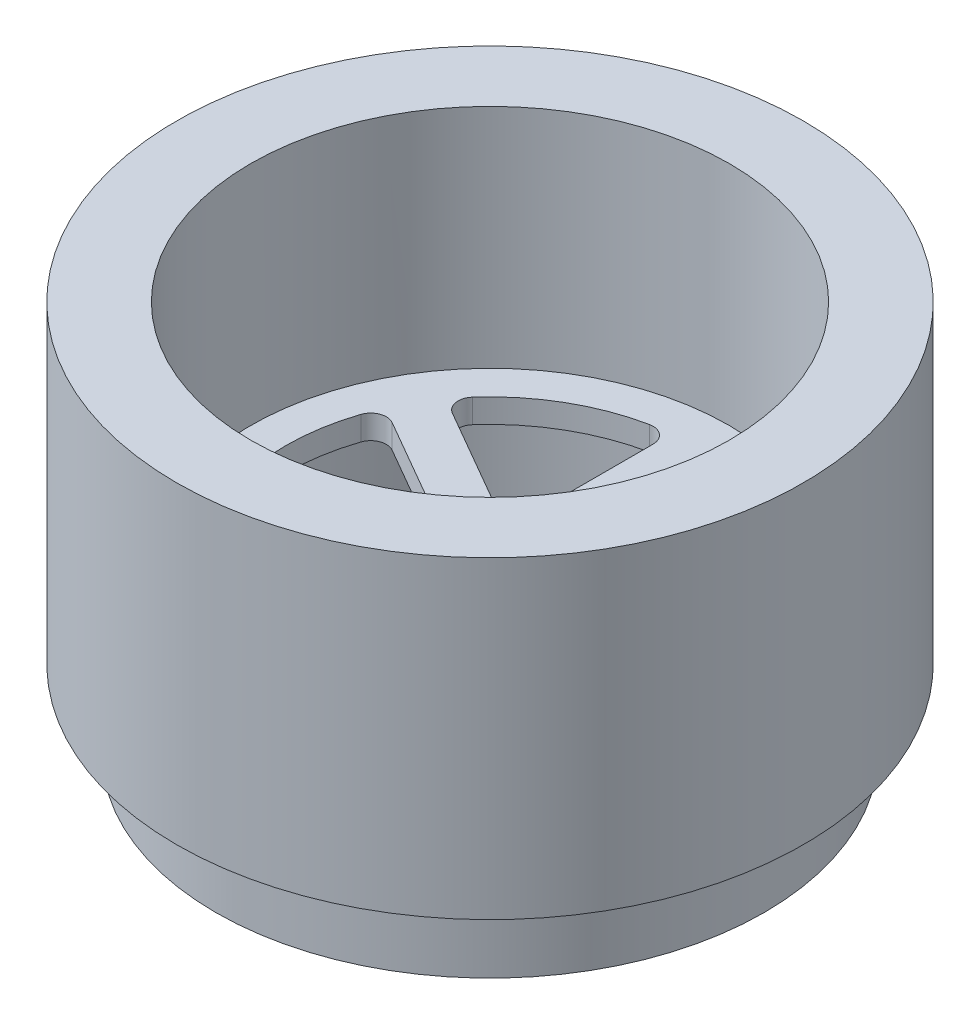
SolidWorks part; units mm, degrees
material "6061-T6 (SS)"
ref_plane "Front Plane" through (0, 0, 0) normal (0, 0, 1) x (1, 0, 0)
ref_plane "Top Plane" through (0, 0, 0) normal (0, 1, 0) x (1, 0, 0)
ref_plane "Right Plane" through (0, 0, 0) normal (1, 0, 0) x (0, 0, -1)
other "Center of Mass"
sketch "Sketch1" plane through (0, 0, 0) normal (0, 1, 0) x (1, 0, 0)
  circle A0 centre (0, 0) radius 20
  circle A1 centre (0, 0) radius 15.28
  dimension "D1" = 30.56
  dimension "D2" = 40
extrude "Boss-Extrude1" add sketch "Sketch1" along normal blind 25
ref_plane "Plane1" through (0, 9, 0) normal (0, -1, 0) x (-1, 0, 0)
sketch "Sketch3" plane through (0, 9, 0) normal (0, -1, 0) x (-1, 0, 0)
  circle A0 centre (0, 0) radius 20
  dimension "D1" = 40
extrude "Boss-Extrude2" add sketch "Sketch3" against normal blind 1.524
sketch "Sketch4" plane through (0, 9, 0) normal (0, -1, 0) x (-1, 0, 0)
  circle A0 centre (0, 0) radius 0.756
  circle A1 centre (0, 0) radius 2
  dimension "D1" = 1.512
extrude "Boss-Extrude3" add sketch "Sketch4" along normal blind 3.5
sketch "Sketch5" plane through (0, 0, 0) normal (0, 1, 0) x (1, 0, 0)
  circle A0 centre (0, 0) radius 17.5
  dimension "D1" = 35
extrude "Cut-Extrude1" cut sketch "Sketch5" along normal blind 5 flip side to cut
sketch "Sketch6" plane through (0, 9, 0) normal (0, -1, 0) x (-1, 0, 0)
  line L0 (1.4079, -4.359) -> (1.4079, -11.8075)
  line L1 (0, 0) -> (6.5253, -11.3021) construction
  line L2 (3.071, -3.3987) -> (9.5217, -7.123)
  circle A0 centre (0, 0) radius 13.0506 construction
  circle A1 centre (0, 0) radius 3.9798 construction
  arc A2 (2.6077, -12.7874) -> (9.7703, -8.652) centre (0, 0) ccw
  arc A3 (1.9243, -3.4836) -> (2.0547, -3.4083) centre (0, 0) ccw
  arc A4 (1.4079, -11.8075) -> (2.6077, -12.7874) centre (2.4079, -11.8075) ccw
  arc A5 (9.5217, -7.123) -> (9.7703, -8.652) centre (9.0217, -7.989) cw
  arc A6 (3.071, -3.3987) -> (2.0547, -3.4083) centre (2.571, -4.2648) ccw
  arc A7 (1.4079, -4.359) -> (1.9243, -3.4836) centre (2.4079, -4.359) cw
  point P13 (1.4079, -12.9744)
  point P14 (10.5322, -7.7065)
  point P17 (2.5198, -3.0805)
  point P20 (1.4079, -3.7225)
  dimension "D1" = 1
  dimension "D2" = 1
  dimension "D3" = 1
  dimension "D4" = 1
extrude "Cut-Extrude2" cut sketch "Sketch6" against normal up to next
pattern_circular "CirPattern1" count 6 over 360 about axis through (0, 5.5, 0) along (0, -1, 0) of "Cut-Extrude2"
